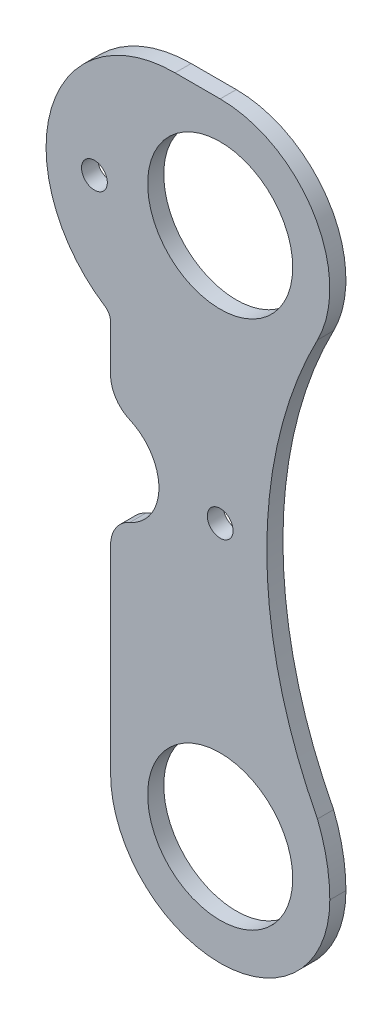
SolidWorks part; units mm, degrees
material "6061 Alloy"
ref_plane "Front Plane" through (0, 0, 0) normal (0, 0, 1) x (1, 0, 0)
ref_plane "Top Plane" through (0, 0, 0) normal (0, 1, 0) x (1, 0, 0)
ref_plane "Right Plane" through (0, 0, 0) normal (1, 0, 0) x (0, 0, -1)
sketch "Sketch1" plane through (0, 0, 0) normal (0, 0, 1) x (1, 0, 0)
  line L0 (0, 0) -> (0, -101.6) construction
  line L1 (21.59, -120.5575) -> (-21.59, -120.5575) construction
  line L2 (-8.89, 25.4) -> (8.89, 25.4)
  line L3 (-21.59, 12.7) -> (-21.59, -117.7751)
  line L5 (21.59, 12.7) -> (21.59, -117.7751)
  line L9 (-23.3829, -122.6853) -> (-33.2033, -134.3394)
  line L10 (-36.322, 25.4) -> (20.828, 25.4) construction
  line L11 (-36.322, 25.4) -> (-36.322, -203.2) construction
  line L12 (-36.322, -203.2) -> (20.828, -203.2) construction
  line L13 (20.828, 25.4) -> (20.828, -203.2) construction
  line L15 (-7.9527, -155.6168) -> (19.7971, -122.6853)
  line L16 (-32.4392, -143.2871) -> (-16.9004, -156.3809)
  circle A0 centre (0, 0) radius 38.1 construction
  circle A1 centre (0, -101.6) radius 38.1 construction
  circle A2 centre (0, 0) radius 14.2875
  circle A3 centre (0, -101.6) radius 14.2875
  arc A6 (8.89, 25.4) -> (21.59, 12.7) centre (8.89, 12.7) cw
  arc A7 (-8.89, 25.4) -> (-21.59, 12.7) centre (-8.89, 12.7) ccw
  circle A10 centre (-18.5321, -142.5501) radius 2.54
  arc A13 (-23.3829, -122.6853) -> (-21.59, -117.7751) centre (-29.21, -117.7751) ccw
  arc A14 (19.7971, -122.6853) -> (21.59, -117.7751) centre (13.97, -117.7751) ccw
  arc A15 (-16.9004, -156.3809) -> (-7.9527, -155.6168) centre (-12.8086, -151.525) ccw
  arc A16 (-33.2033, -134.3394) -> (-32.4392, -143.2871) centre (-28.3474, -138.4312) ccw
  circle A17 centre (0, -50.8) radius 2.54
  point P13 (-192.705, 39.2708)
  point P20 (21.59, 25.4)
  point P23 (-21.59, 25.4)
  point P31 (-36.322, -138.0404)
  dimension "D2" = 76.2
  dimension "D3" = 76.2
  dimension "D4" = 28.575
  dimension "D5" = 28.575
  dimension "D10" = 228.6
  dimension "D11" = 36.322
  dimension "D13" = 5.08
  dimension "D19" = 6.35
  dimension "D20" = 7.62
  dimension "D21" = 12.7
  dimension "D22" = 5.08
  dimension "D1" = 101.6
  dimension "D6" = 43.18
  dimension "D7" = 21.59
  dimension "D8" = 25.4
  dimension "D9" = 57.15
  dimension "D12" = 25.4
  dimension "D14" = 33.02
  dimension "D15" = 16.51
  dimension "D16" = 21.59
  dimension "D17" = 9.525
  dimension "D18" = 18.9575
extrude "Boss-Extrude1" add sketch "Sketch1" along normal blind 3.175
sketch "Sketch2" plane through (0, 0, 0) normal (0, 0, 1) x (1, 0, 0)
  line L0 (-21.59, -41.275) -> (-21.59, -60.325)
  line L1 (0, 0) -> (0, -101.6) construction
  line L4 (21.59, -117.7751) -> (21.59, 12.7) construction
  line L5 (-21.59, -50.8) -> (97.79, -50.8) construction
  line L6 (-21.59, 12.7) -> (-21.59, -117.7751) construction
  line L7 (0, 0) -> (-39.9512, 0) construction
  line L9 (16.51, -115.5122) -> (-17.5013, -155.8745)
  line L10 (-32.4392, -143.2871) -> (-16.9004, -156.3809) construction
  line L11 (-7.9527, -155.6168) -> (19.7971, -122.6853) construction
  line L13 (27.94, -121.6567) -> (-7.7896, -164.0581)
  line L14 (-7.7896, -164.0581) -> (-17.5013, -155.8745)
  line L15 (27.94, -121.6567) -> (27.94, 0)
  line L16 (27.94, 0) -> (21.59, 0)
  arc A1 (19.1591, -91.6472) -> (19.1591, -9.9528) centre (97.79, -50.8) cw
  arc A2 (-21.59, -60.325) -> (-21.59, -41.275) centre (-21.59, -50.8) ccw
  arc A3 (21.59, 0) -> (19.1591, -9.9528) centre (0, 0) cw
  arc A4 (21.59, -101.6) -> (19.1591, -91.6472) centre (0, -101.6) ccw
  arc A5 (21.59, -101.6) -> (16.51, -115.5122) centre (0, -101.6) cw
  dimension "D2" = 12.7
  dimension "D3" = 50.8
  dimension "D4" = 6.35
  dimension "D1" = 76.2
  dimension "D5" = 19.05
extrude "Cut-Extrude1" cut sketch "Sketch2" along normal through all contours A1 A3 L16 L15 L13 L14 L9 A5 A4 | L0 A2
sketch "Sketch3" plane through (0, 0, 3.175) normal (0, 0, 1) x (1, 0, 0)
  line L0 (-27.3514, -127.3948) -> (-36.0255, -137.6886)
  line L3 (-27.3514, -127.3948) -> (-7.5576, -144.074)
  line L4 (-23.3829, -122.6853) -> (-33.2033, -134.3394) construction
  line L5 (16.51, -115.5122) -> (-17.5013, -155.8745) construction
  line L7 (-35.4064, -144.9387) -> (-24.4031, -154.2106)
  line L8 (-23.3829, -122.6853) -> (-33.2033, -134.3394) construction
  line L9 (-7.5576, -144.074) -> (-15.4554, -153.4465)
  line L10 (-32.4392, -143.2871) -> (-17.5013, -155.8745) construction
  circle A2 centre (-18.5321, -142.5501) radius 2.54
  circle A3 centre (-18.5321, -142.5501) radius 2.54 construction
  arc A5 (-36.0255, -137.6886) -> (-35.4064, -144.9387) centre (-32.0909, -141.0041) ccw
  arc A6 (-24.4031, -154.2106) -> (-15.4554, -153.4465) centre (-20.3113, -149.3547) ccw
  dimension "D2" = 6.35
  dimension "D3" = 5.1453
  dimension "D1" = 3.175
fillet "Fillet3" radius 6.35 2 edges at (-21.59, -41.275, 1.5875) (-21.59, -60.325, 1.5875)
extrude "Boss-Extrude3" add sketch "Sketch3" against normal blind 3.175
sketch "Sketch6" plane through (0, 0, 3.175) normal (0, 0, 1) x (1, 0, 0)
  line L0 (-35.4064, -144.9387) -> (-63.6204, -121.1641)
  line L1 (-63.6204, -121.1641) -> (-51.345, -106.5965)
  line L2 (-51.345, -106.5965) -> (-27.0656, -127.0555)
  line L4 (-35.4064, -144.9387) -> (-24.4031, -154.2106) construction
  line L5 (-23.3829, -122.6853) -> (-36.0255, -137.6886) construction
  line L6 (-35.4064, -144.9387) -> (-27.0656, -127.0555)
  circle A0 centre (-52.6268, -117.9721) radius 2.54
  dimension "D4" = 5.08
  dimension "D1" = 31.75
  dimension "D2" = 9.525
  dimension "1" = 19.05
  dimension "D3" = 6.35
extrude "Boss-Extrude4" add sketch "Sketch6" against normal blind 3.175
fillet "Fillet2" radius 6.35 3 edges at (-63.6204, -121.1641, 1.5875) (-51.345, -106.5965, 1.5875) (-27.0656, -127.0555, 1.5875)
sketch "Sketch7" plane through (0, 0, 3.175) normal (0, 0, 1) x (1, 0, 0)
  line L0 (-21.59, 12.7) -> (-21.59, -36.2503) construction
  line L1 (21.59, 0) -> (21.59, 12.7) construction
  line L2 (-21.59, 0) -> (21.59, 0) construction
  line L3 (-21.59, 0) -> (-21.59, 31.75)
  line L4 (-21.59, 31.75) -> (21.59, 31.75)
  line L5 (21.59, 31.75) -> (21.59, 0)
  line L6 (8.89, 25.4) -> (-8.89, 25.4) construction
  arc A0 (-21.59, 0) -> (21.59, 0) centre (0, 0) cw
  dimension "D1" = 6.35
extrude "Cut-Extrude2" cut sketch "Sketch7" against normal through all
sketch "Sketch10" plane through (0, 0, 3.175) normal (0, 0, 1) x (1, 0, 0)
  line L0 (16.51, -115.5122) -> (-17.5013, -155.8745) construction
  line L1 (-18.1519, -155.3263) -> (-17.3615, -157.512)
  line L2 (-17.3615, -157.512) -> (-14.3757, -156.4323)
  line L3 (-14.3757, -156.4323) -> (-15.4554, -153.4465)
  line L5 (-18.1519, -155.3263) -> (-17.5013, -155.8745) construction
  circle A0 centre (-20.3113, -149.3547) radius 6.35 construction
  arc A1 (-24.4031, -154.2106) -> (-18.1519, -155.3263) centre (-20.3113, -149.3547) ccw construction
  arc A2 (-18.1519, -155.3263) -> (-15.4554, -153.4465) centre (-20.3113, -149.3547) ccw
  dimension "D1" = 3.175
  dimension "D2" = 30
extrude "Cut-Extrude3" cut sketch "Sketch10" against normal through all
sketch "Sketch12" plane through (0, 0, 3.175) normal (0, 0, 1) x (1, 0, 0)
  line L0 (-21.59, -65.3497) -> (-21.59, -117.7751) construction
  line L1 (-21.59, -101.6) -> (-72.39, -101.6)
  line L2 (-72.39, -101.6) -> (-72.39, -165.1)
  line L3 (-72.39, -165.1) -> (16.51, -165.1)
  line L4 (16.51, -165.1) -> (16.51, -115.5122)
  arc A2 (16.51, -115.5122) -> (-21.59, -101.6) centre (0, -101.6) cw
  dimension "D1" = 63.5
  dimension "D2" = 88.9
extrude "Cut-Extrude4" cut sketch "Sketch12" against normal through all
sketch "Sketch15" plane through (0, 0, 3.175) normal (0, 0, 1) x (1, 0, 0)
  line L0 (-21.59, 0) -> (-21.59, -36.2503) construction
  line L5 (-21.59, -29.21) -> (-21.59, 0)
  line L7 (0, 21.59) -> (-16.6076, 6.9565)
  line L8 (-16.6076, 6.9565) -> (-12.5785, -28.9408)
  line L9 (-8.89, 21.59) -> (0, 21.59)
  arc A0 (-12.5785, -28.9408) -> (-34.29, -3.81) centre (-8.89, -3.81) cw
  arc A1 (-8.89, 21.59) -> (-34.29, -3.81) centre (-8.89, -3.81) ccw
  circle A2 centre (-24.765, -3.81) radius 2.54
  arc A3 (19.1591, -9.9528) -> (-21.59, 0) centre (0, 0) ccw construction
  point P10 (0, 0)
  point P11 (0, 0)
  arc M10 (19.1591, -9.9528) -> (-21.59, 0) centre (0, 0) ccw
  line M11 (-21.59, 0) -> (-21.59, -36.2503)
  dimension "D1" = 12.7
  dimension "D4" = 3.175
  dimension "D3" = 5.08
  dimension "D2" = 25.4
extrude "Boss-Extrude8" add sketch "Sketch15" against normal blind 3.175 contours L9 A1 A0 A2 M11 M10 region at (-24.9677, -0.0937, 3.175)
fillet "Fillet4" radius 2.54 1 edges at (-21.59, -25.807, 1.5875)
sketch "Sketch16" plane through (0, 0, 3.175) normal (0, 0, 1) x (1, 0, 0)
  line L1 (0, -102.5377) -> (0, -93.0735) construction
  line L2 (0, -101.6) -> (-11.1927, -101.6) construction
  line L4 (-21.59, -101.6) -> (-1.4895, -121.7005)
  line L5 (-1.4895, -121.7005) -> (4.5179, -121.7005)
  line L6 (4.5179, -121.7005) -> (21.59, -101.6)
  line L7 (-21.59, -65.3497) -> (-21.59, -101.6) construction
  line L8 (-21.59, -101.6) -> (-21.59, -104.2391)
  line L9 (21.59, -101.6) -> (21.59, -104.2391)
  arc A0 (-21.59, -104.2391) -> (21.59, -104.2391) centre (0, -104.2391) ccw
  arc A1 (-21.59, -101.6) -> (19.1591, -91.6472) centre (0, -101.6) ccw construction
  dimension "D1" = 2.6391
extrude "Boss-Extrude9" add sketch "Sketch16" against normal through all contours L6 L9 A0 L8 L4 L5
sketch "Sketch17" plane through (0, 0, 3.175) normal (0, 0, 1) x (1, 0, 0)
  circle A0 centre (0, -101.6) radius 14.2875
  circle A1 centre (0, -101.6) radius 14.2875 construction
extrude "Boss-Extrude10" add sketch "Sketch17" against normal through all
sketch "Sketch19" plane through (0, 0, 3.175) normal (0, 0, 1) x (1, 0, 0)
  line L0 (21.59, -104.2391) -> (21.59, -95.9079) construction
  line L1 (19.1591, -91.6472) -> (21.59, -91.6472)
  line L2 (21.59, -91.6472) -> (21.59, -104.2391)
  arc A0 (19.1591, -91.6472) -> (21.59, -104.2391) centre (-12.2375, -104.2391) cw
extrude "Cut-Extrude5" cut sketch "Sketch19" against normal through all
sketch "Sketch20" plane through (0, 0, 3.175) normal (0, 0, 1) x (1, 0, 0)
  circle A0 centre (0, -104.2391) radius 14.2875
  arc A1 (-21.59, -104.2391) -> (21.59, -104.2391) centre (0, -104.2391) ccw construction
  dimension "D1" = 28.575
extrude "Cut-Extrude6" cut sketch "Sketch20" against normal through all
